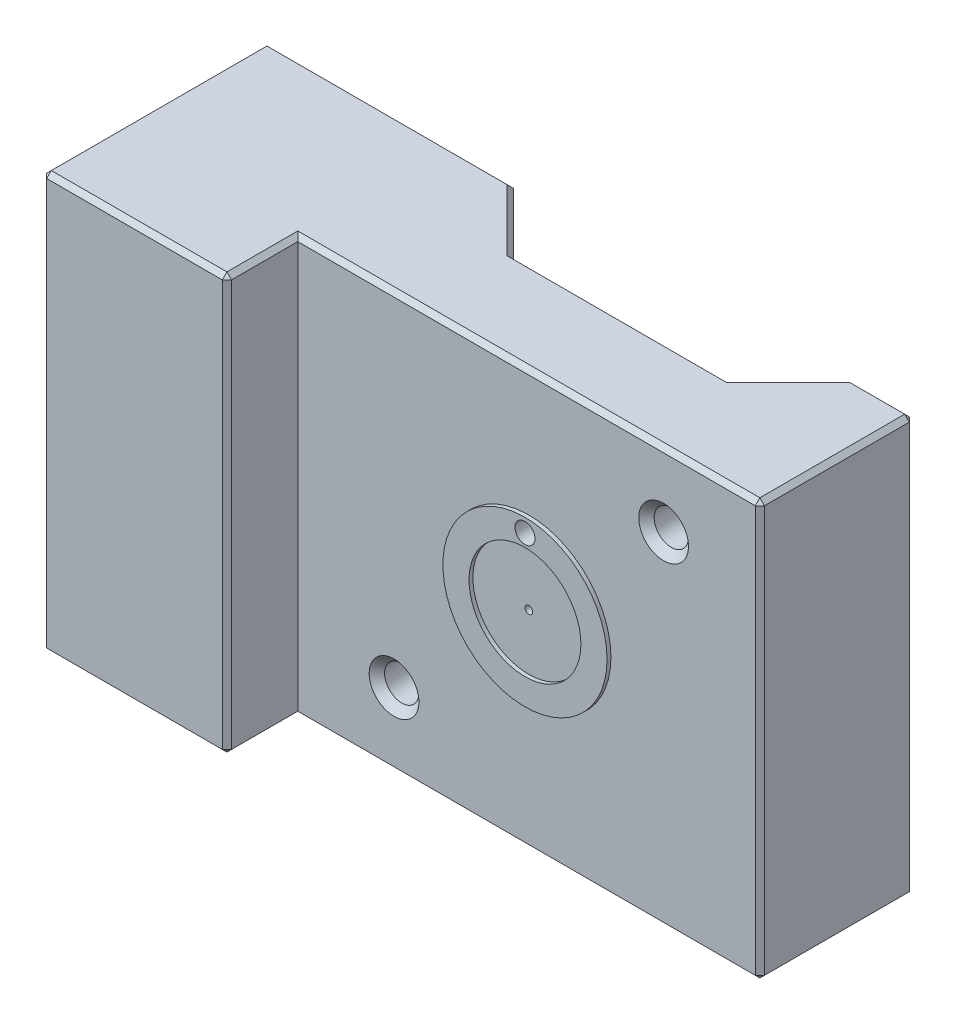
SolidWorks part; units mm, degrees
ref_plane "Front Plane" through (0, 0, 0) normal (0, 0, 1) x (1, 0, 0)
ref_plane "Top Plane" through (0, 0, 0) normal (0, 1, 0) x (1, 0, 0)
ref_plane "Right Plane" through (0, 0, 0) normal (1, 0, 0) x (0, 0, -1)
sketch "Sketch1" plane through (0, 0, 0) normal (0, 0, 1) x (1, 0, 0)
  line L0 (-3, 3) -> (27, 3)
  line L1 (0, 0) -> (24, 0) construction
  line L2 (0, 0) -> (0, -21) construction
  line L3 (0, -21) -> (24, -21) construction
  line L4 (24, 0) -> (24, -21) construction
  line L5 (27, 3) -> (27, -24)
  line L6 (-3, -24) -> (27, -24)
  line L7 (-3, 3) -> (-3, -24)
  dimension "D1" = 21
  dimension "D2" = 24
  dimension "D3" = 3
extrude "Boss-Extrude1" add sketch "Sketch1" against normal blind 10 contours L0 L5 L6 L7
sketch "Sketch2" plane through (0, 0, 0) normal (0, 0, 1) x (1, 0, 0)
  line L0 (-3, 3) -> (27, -24) construction
  line L1 (12, -10.5) -> (12, 3) construction
  line L2 (-3, 3) -> (27, 3) construction
  line L3 (12, -10.5) -> (27, -10.5) construction
  line L4 (27, 3) -> (27, -24) construction
  line L5 (3.25, -19.25) -> (20.75, -1.75) construction
  circle A0 centre (12, -10.5) radius 3.43 construction
  circle A1 centre (12, -10.5) radius 1.145 construction
  circle A2 centre (12, -10.5) radius 1.78 construction
  circle A5 centre (12, -10.5) radius 0.25
  circle A7 centre (12, -10.5) radius 5.46 construction
  circle A8 centre (12, -10.5) radius 3.6318
  circle A9 centre (12, -10.5) radius 5.3293
  circle A10 centre (20.75, -1.75) radius 1.115
  circle A11 centre (3.25, -19.25) radius 1.115
  point P18 (12, -10.5)
  point P25 (9, -11.145)
  dimension "D1" = 6.86
  dimension "D2" = 2.29
  dimension "D3" = 3.56
  dimension "D6" = 0.5
  dimension "D7" = 10.92
  dimension "D10" = 2.23
  dimension "D8" = 17.5
  dimension "D9" = 17.5
extrude "Cut-Extrude1" cut sketch "Sketch2" against normal up to surface (10 mm away) contours A11 | A10 up to face at (12, -10.5, -10)
extrude "Boss-Extrude2" add sketch "Sketch2<4>" along normal blind 0.25 contours A8 | A9
sketch "Sketch2<4>" plane through (0, 0, 0) normal (0, 0, 1) x (1, 0, 0) same geometry as "Sketch2"
extrude "Cut-Extrude2" cut sketch "Sketch2<5>" against normal up to surface (10 mm away) contours A5 up to face at (4.365, -19.25, -10)
sketch "Sketch2<5>" plane through (0, 0, 0) normal (0, 0, 1) x (1, 0, 0) same geometry as "Sketch2"
sketch "Sketch4" plane through (0, 0, 0.25) normal (0, 0, 1) x (1, 0, 0)
  circle A0 centre (12, -6.055) radius 0.65
  dimension "D1" = 1.3
extrude "Cut-Extrude3" cut sketch "Sketch4" against normal blind 3
sketch "Sketch3" plane through (-3, 0, 0) normal (-1, 0, 0) x (0, 0, 1)
  line L0 (-10, 3) -> (0, 3) construction
  line L4 (0, -24) -> (0, -28.2366) construction
  line L5 (0, 3) -> (0, -24) construction
  line L6 (-10, -24) -> (0, -24) construction
  circle A0 centre (-2.7, -6.7) radius 1.5
  circle A1 centre (-2.7, -6.7) radius 4.2164 construction
  point P0 (-2.7, -6.7)
  dimension "D1" = 3
  dimension "D4" = 8.4328
  dimension "D3" = 1.2
  dimension "D2" = 9.7
sketch "Sketch5" plane through (-3, 0, 0) normal (-1, 0, 0) x (0, 0, 1)
  line L0 (-10, -24) -> (0, -24) construction
  line L1 (-10, 3) -> (4.6, 3)
  line L2 (-10, 3) -> (-10, -24)
  line L3 (-10, -24) -> (4.6, -24)
  line L4 (4.6, 3) -> (4.6, -24)
  circle A0 centre (-2.7, -6.7) radius 4.2164 construction
  dimension "D1" = 3.0836
  dimension "D2" = 3.0836
extrude "Boss-Extrude3" add sketch "Sketch5" along normal blind 12
extrude "Cut-Extrude4" cut sketch "Sketch3" along normal up to surface (12 mm away) and the other way blind 15 up to face at (-15, -10.5, -2.7)
sketch "Sketch7" plane through (-15, 0, 0) normal (-1, 0, 0) x (0, 0, 1)
  circle A0 centre (-2.7, -6.7) radius 4.2164
  dimension "D1" = 8.4328
extrude "Cut-Extrude5" cut sketch "Sketch7" against normal blind 9.8
ref_point "Point1"
ref_point "Point2"
ref_plane "Plane1" through (0, -6.7, 0) normal (0, -1, 0) x (-1, 0, 0)
sketch "Sketch8" plane through (0, 0, -10) normal (0, 0, -1) x (-1, 0, 0)
  line L0 (15, -24) -> (-27, -24) construction
  line L1 (-23, 3) -> (-1, 3)
  line L2 (-23, 3) -> (-23, -24)
  line L3 (-23, -24) -> (-1, -24)
  line L4 (-1, 3) -> (-1, -24)
  line L5 (-27, 3) -> (-27, -24) construction
  dimension "D1" = 4
  dimension "D2" = 4
extrude "Cut-Extrude6" cut sketch "Sketch8" against normal blind 4
chamfer "Chamfer1" distance 4 angle 45 2 edges at (1, -10.5, -6) (23, -10.5, -6)
sketch "Sketch9" plane through (0, 0, -6) normal (0, 0, -1) x (-1, 0, 0)
  circle A0 centre (-12, -10.5) radius 2
  dimension "D1" = 4
extrude "Cut-Extrude7" cut sketch "Sketch9" against normal blind 2.5
chamfer "Chamfer2" distance 2.5 angle 45 1 edges at (10, -10.5, -6)
chamfer "Chamfer3" distance 0.3 angle 45 25 edges at (-3, 3, 2.3) (3, 3, -8) (12, 3, -6) (-3, -24, 2.3) (27, -24, -5) (12, -24, 0) (27, -10.5, 0) (12, 3, 0) (27, 3, -5) (12, -24, -6) (3, -24, -8) (-9, -24, 4.6) (-9, 3, 4.6) (-15, 3, -2.7) (-15, -10.5, 4.6) (-15, -24, -2.7) (-7, 3, -10) (-15, -10.5, -10) (-7, -24, -10) (-3, -10.5, 4.6) (25, 3, -10) (25, -24, -10) (27, -10.5, -10) (21, 3, -8) (21, -24, -8)
chamfer "Chamfer4" distance 0.5 angle 45 2 edges at (4.365, -19.25, 0) (21.865, -1.75, 0)
equation "\"D2@Sketch5\"=\"D1@Sketch5\""
equation "\"D2@Sketch8\"=\"D1@Sketch8\""
